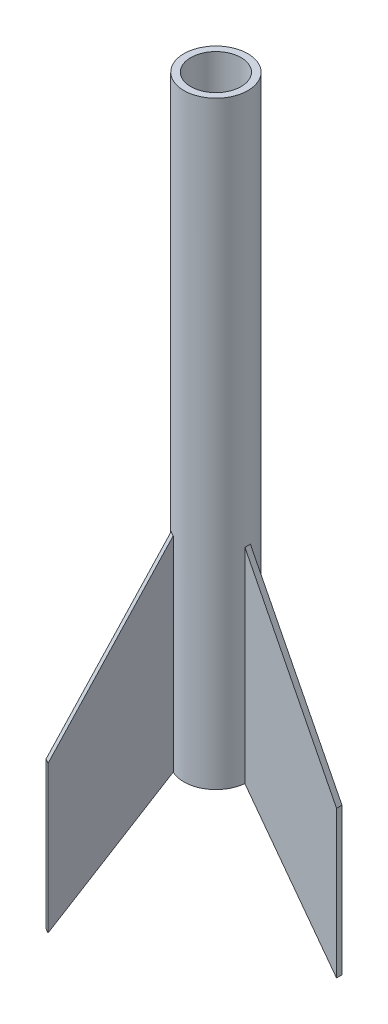
SolidWorks part; units mm, degrees
ref_plane "Front Plane" through (0, 0, 0) normal (0, 0, 1) x (1, 0, 0)
ref_plane "Top Plane" through (0, 0, 0) normal (0, 1, 0) x (1, 0, 0)
ref_plane "Right Plane" through (0, 0, 0) normal (1, 0, 0) x (0, 0, -1)
sketch3d "3DSketch1" plane through (0, 0, 0) normal (0, 0, 1) x (1, 0, 0)
sketch "Sketch2" plane through (-2.4658, 0, -0.081) normal (0, 1, 0) x (1, 0, 0)
  circle A0 centre (2.4117, 0) radius 11.75
  circle A1 centre (2.4117, 0) radius 9.25
  dimension "D1" = 23.5
  dimension "D2" = 18.5
extrude "Boss-Extrude1" add sketch "Sketch2" along normal blind 220
ref_plane "Plane2" through (0, 60, 0) normal (0, 1, 0) x (1, 0, 0)
sketch "Sketch5" plane through (0, 60, 0) normal (0, 1, 0) x (1, 0, 0)
  circle A0 centre (-0.0541, 0.081) radius 9.5
  circle A1 centre (-0.0541, 0.081) radius 4.625
  dimension "D1" = 19
  dimension "D2" = 9.25
extrude "Boss-Extrude2" add sketch "Sketch5" along normal blind 12
sketch "Sketch7" plane through (0, 0, 0) normal (0, 0, 1) x (1, 0, 0)
  line L4 (11.6959, 75.2) -> (9.8282, 75.2)
  line L9 (9.8282, 75.2) -> (10.6959, 0)
  line L10 (10.6959, 0) -> (11.6959, 0)
  line L11 (11.6959, 75.2) -> (45.3473, 9)
  line L12 (11.6959, 0) -> (11.6959, 220) construction
  line L13 (45.3473, 9) -> (45.3473, -45)
  line L14 (45.3473, -45) -> (11.6959, 0)
  line L15 (12.925, 0) -> (-12.925, 0) construction
  line L16 (11.6959, 0) -> (11.6959, 75.2) construction
  dimension "D1" = 1
extrude "Boss-Extrude3" add sketch "Sketch7" along normal blind 1 and the other way blind 1 contours L11 L13 L14 L10 L9 L4
pattern_circular "CirPattern1" count 3 every 120 about axis through (-0.0541, 220, -0.081) along (0, -1, 0) of "Boss-Extrude3"
